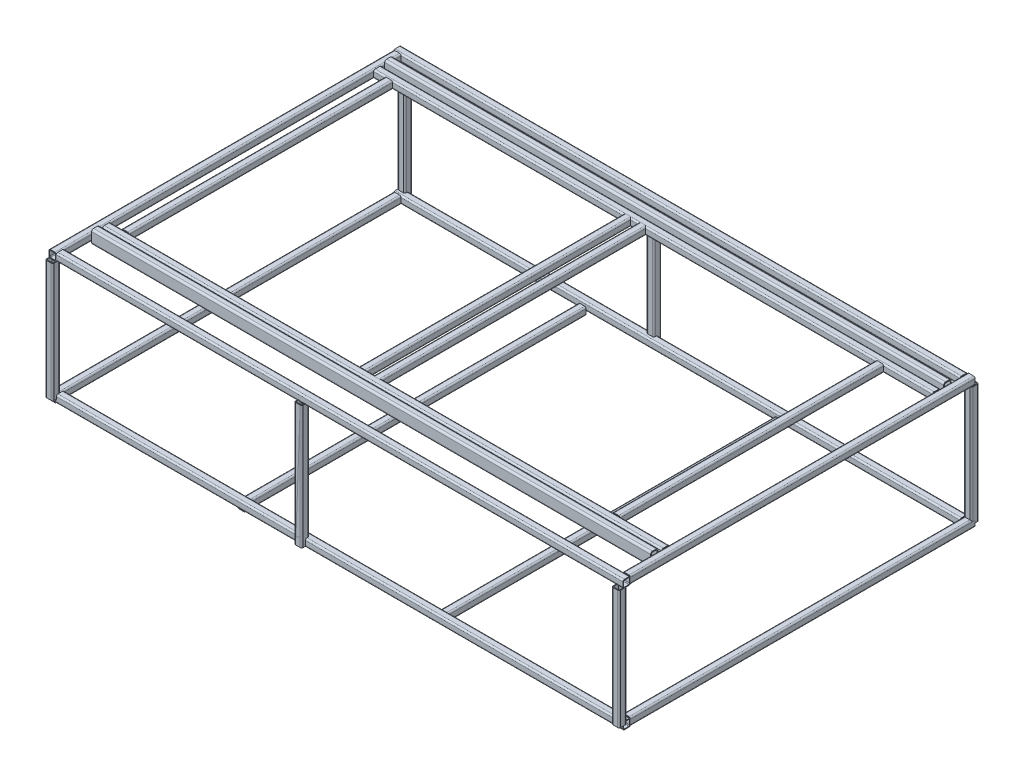
SolidWorks part; units mm, degrees
material "Beech"
ref_plane "Front Plane" through (0, 0, 0) normal (0, 0, 1) x (1, 0, 0)
ref_plane "Top Plane" through (0, 0, 0) normal (0, 1, 0) x (1, 0, 0)
ref_plane "Right Plane" through (0, 0, 0) normal (1, 0, 0) x (0, 0, -1)
sketch "Sketch1" plane through (0, 0, 0) normal (0, 1, 0) x (1, 0, 0)
  line L1 (-1500, 912.5) -> (1500, 912.5)
  line L2 (-1500, 912.5) -> (-1500, -912.5)
  line L3 (-1500, -912.5) -> (1500, -912.5)
  line L4 (1500, 912.5) -> (1500, -912.5)
  line L5 (-1500, 912.5) -> (1500, -912.5) construction
  line L6 (-1500, -912.5) -> (1500, 912.5) construction
  point P0 (0, 0)
  dimension "D1" = 3000
  dimension "D2" = 1825
other "Square tube 40 X 40 X 4(1)" corner treatment butt1
ref_plane "Plane1" through (-1500, 0, -912.5) normal (0, 0, 1) x (1, 0, 0)
sketch "Sketch13" plane through (-1500, 0, -912.5) normal (0, 0, 1) x (1, 0, 0)
  line L0 (-12, -16) -> (12, -16)
  line L1 (-16, -12) -> (-16, 12)
  line L2 (12, 16) -> (-12, 16)
  line L3 (16, 12) -> (16, -12)
  line L4 (-12, -20) -> (12, -20)
  line L5 (-20, -12) -> (-20, 12)
  line L6 (12, 20) -> (-12, 20)
  line L7 (20, 12) -> (20, -12)
  arc A0 (20, 12) -> (12, 20) centre (12, 12) ccw
  arc A1 (12, -20) -> (20, -12) centre (12, -12) ccw
  arc A2 (-20, -12) -> (-12, -20) centre (-12, -12) ccw
  arc A3 (-12, 20) -> (-20, 12) centre (-12, 12) ccw
  arc A4 (-12, 16) -> (-16, 12) centre (-12, 12) ccw
  arc A5 (16, 12) -> (12, 16) centre (12, 12) ccw
  arc A6 (12, -16) -> (16, -12) centre (12, -12) ccw
  arc A7 (-16, -12) -> (-12, -16) centre (-12, -12) ccw
  point P0 (-20, 0)
  point P1 (20, 0)
  point P2 (0, 20)
  point P3 (0, -20)
  point P4 (0, 0)
  point P5 (-20, -20)
  point P6 (20, -20)
  point P7 (20, 20)
  point P8 (-20, 20)
  point P33 (0, 0)
  dimension "D1" = 8
  dimension "Thickness" = 4
  dimension "V_leg" = 40
sketch "Sketch15" plane through (0, 0, 0) normal (0, 1, 0) x (1, 0, 0)
  line L0 (-1480, 826) -> (1480, 826)
  line L1 (-1480, -932.5) -> (-1480, 892.5) construction
  line L2 (1480, 932.5) -> (1480, -892.5) construction
  line L3 (-1480, -726) -> (1480, -726)
  line L4 (1520, -892.5) -> (-1480, -892.5) construction
  line L5 (-1520, 892.5) -> (1480, 892.5) construction
  dimension "D1" = 166.5
  dimension "D2" = 66.5
other "Rectangular tube 70 X 40 X 5(1)" corner treatment butt1
ref_plane "Plane2" through (-1480, 0, -826) normal (1, 0, 0) x (0, 0, -1)
sketch "Sketch17" plane through (-1480, 0, -826) normal (1, 0, 0) x (0, 0, -1)
  line L0 (-10, -30) -> (10, -30)
  line L1 (-15, -25) -> (-15, 25)
  line L2 (10, 30) -> (-10, 30)
  line L3 (15, 25) -> (15, -25)
  line L4 (-10, -35) -> (10, -35)
  line L5 (-20, -25) -> (-20, 25)
  line L6 (10, 35) -> (-10, 35)
  line L7 (20, 25) -> (20, -25)
  arc A0 (20, 25) -> (10, 35) centre (10, 25) ccw
  arc A1 (10, -35) -> (20, -25) centre (10, -25) ccw
  arc A2 (-20, -25) -> (-10, -35) centre (-10, -25) ccw
  arc A3 (-10, 35) -> (-20, 25) centre (-10, 25) ccw
  arc A4 (-10, 30) -> (-15, 25) centre (-10, 25) ccw
  arc A5 (15, 25) -> (10, 30) centre (10, 25) ccw
  arc A6 (10, -30) -> (15, -25) centre (10, -25) ccw
  arc A7 (-15, -25) -> (-10, -30) centre (-10, -25) ccw
  point P0 (0, 35)
  point P1 (20, 0)
  point P2 (0, -35)
  point P3 (-20, 0)
  point P4 (-20, 35)
  point P5 (20, 35)
  point P6 (20, -35)
  point P7 (-20, -35)
  point P8 (0, 0)
  point P33 (0, 0)
  dimension "D1" = 10
  dimension "Thickness" = 5
  dimension "V_leg" = 70
  dimension "H_leg" = 40
sketch "Sketch18" plane through (0, 0, 0) normal (0, 1, 0) x (1, 0, 0)
  line L0 (-1480, 767.5) -> (1480, 767.5)
  line L1 (-1480, -932.5) -> (-1480, 892.5) construction
  line L2 (1480, 932.5) -> (1480, -892.5) construction
  line L3 (1480, -667.5) -> (-1480, -667.5)
  line L5 (1480, 806) -> (-1480, 806) construction
  line L6 (1480, -706) -> (-1480, -706) construction
  dimension "D1" = 38.5
  dimension "D2" = 38.5
ref_plane "Plane3" through (-1480, 0, -767.5) normal (1, 0, 0) x (0, 0, -1)
other "Square tube 40 X 40 X 4(2)" corner treatment butt1
ref_plane "Plane4" through (-1480, 0, -767.5) normal (1, 0, 0) x (0, 0, -1)
sketch "Sketch110" plane through (-1480, 0, -767.5) normal (1, 0, 0) x (0, 0, -1)
  line L0 (-12, -16) -> (12, -16)
  line L1 (-16, -12) -> (-16, 12)
  line L2 (12, 16) -> (-12, 16)
  line L3 (16, 12) -> (16, -12)
  line L4 (-12, -20) -> (12, -20)
  line L5 (-20, -12) -> (-20, 12)
  line L6 (12, 20) -> (-12, 20)
  line L7 (20, 12) -> (20, -12)
  arc A0 (20, 12) -> (12, 20) centre (12, 12) ccw
  arc A1 (12, -20) -> (20, -12) centre (12, -12) ccw
  arc A2 (-20, -12) -> (-12, -20) centre (-12, -12) ccw
  arc A3 (-12, 20) -> (-20, 12) centre (-12, 12) ccw
  arc A4 (-12, 16) -> (-16, 12) centre (-12, 12) ccw
  arc A5 (16, 12) -> (12, 16) centre (12, 12) ccw
  arc A6 (12, -16) -> (16, -12) centre (12, -12) ccw
  arc A7 (-16, -12) -> (-12, -16) centre (-12, -12) ccw
  point P0 (-20, 0)
  point P1 (20, 0)
  point P2 (0, 20)
  point P3 (0, -20)
  point P4 (0, 0)
  point P5 (-20, -20)
  point P6 (20, -20)
  point P7 (20, 20)
  point P8 (-20, 20)
  point P33 (0, 0)
  dimension "D1" = 8
  dimension "Thickness" = 4
  dimension "V_leg" = 40
sketch "Sketch111" plane through (0, 0, 0) normal (0, 1, 0) x (1, 0, 0)
  line L0 (-1400, 747.5) -> (-1400, -647.5)
  line L1 (1480, 747.5) -> (-1480, 747.5) construction
  line L2 (1480, -647.5) -> (-1480, -647.5) construction
  line L3 (1200, 747.5) -> (1200, -647.5)
  line L5 (-1480, -932.5) -> (-1480, 892.5) construction
  line L6 (1480, 932.5) -> (1480, -892.5) construction
  dimension "D1" = 80
  dimension "D2" = 280
other "Square tube 40 X 40 X 4(3)" corner treatment butt1
ref_plane "Plane5" through (1200, 0, -747.5) normal (0, 0, 1) x (1, 0, 0)
sketch "Sketch112" plane through (1200, 0, -747.5) normal (0, 0, 1) x (1, 0, 0)
  line L0 (-12, -16) -> (12, -16)
  line L1 (-16, -12) -> (-16, 12)
  line L2 (12, 16) -> (-12, 16)
  line L3 (16, 12) -> (16, -12)
  line L4 (-12, -20) -> (12, -20)
  line L5 (-20, -12) -> (-20, 12)
  line L6 (12, 20) -> (-12, 20)
  line L7 (20, 12) -> (20, -12)
  arc A0 (20, 12) -> (12, 20) centre (12, 12) ccw
  arc A1 (12, -20) -> (20, -12) centre (12, -12) ccw
  arc A2 (-20, -12) -> (-12, -20) centre (-12, -12) ccw
  arc A3 (-12, 20) -> (-20, 12) centre (-12, 12) ccw
  arc A4 (-12, 16) -> (-16, 12) centre (-12, 12) ccw
  arc A5 (16, 12) -> (12, 16) centre (12, 12) ccw
  arc A6 (12, -16) -> (16, -12) centre (12, -12) ccw
  arc A7 (-16, -12) -> (-12, -16) centre (-12, -12) ccw
  point P0 (-20, 0)
  point P1 (20, 0)
  point P2 (0, 20)
  point P3 (0, -20)
  point P4 (0, 0)
  point P5 (-20, -20)
  point P6 (20, -20)
  point P7 (20, 20)
  point P8 (-20, 20)
  point P33 (0, 0)
  dimension "D1" = 8
  dimension "Thickness" = 4
  dimension "V_leg" = 40
sketch "Sketch113" plane through (0, 0, 0) normal (0, 1, 0) x (1, 0, 0)
  line L0 (-140, 755.5) -> (-140, -651.5)
  line L1 (1480, 755.5) -> (-1480, 755.5) construction
  line L2 (1480, -651.5) -> (-1480, -651.5) construction
  line L3 (-60, 755.5) -> (-60, -655.5)
  line L4 (1480, -655.5) -> (-1480, -655.5) construction
  line L5 (-1380, -647.5) -> (-1380, 747.5) construction
  line L6 (1180, -647.5) -> (1180, 747.5) construction
  dimension "D1" = 1240
  dimension "D2" = 1240
other "Square tube 40 X 40 X 4(4)" corner treatment butt1
ref_plane "Plane6" through (-60, 0, -755.5) normal (0, 0, 1) x (1, 0, 0)
sketch "Sketch114" plane through (-60, 0, -755.5) normal (0, 0, 1) x (1, 0, 0)
  line L0 (-12, -16) -> (12, -16)
  line L1 (-16, -12) -> (-16, 12)
  line L2 (12, 16) -> (-12, 16)
  line L3 (16, 12) -> (16, -12)
  line L4 (-12, -20) -> (12, -20)
  line L5 (-20, -12) -> (-20, 12)
  line L6 (12, 20) -> (-12, 20)
  line L7 (20, 12) -> (20, -12)
  arc A0 (20, 12) -> (12, 20) centre (12, 12) ccw
  arc A1 (12, -20) -> (20, -12) centre (12, -12) ccw
  arc A2 (-20, -12) -> (-12, -20) centre (-12, -12) ccw
  arc A3 (-12, 20) -> (-20, 12) centre (-12, 12) ccw
  arc A4 (-12, 16) -> (-16, 12) centre (-12, 12) ccw
  arc A5 (16, 12) -> (12, 16) centre (12, 12) ccw
  arc A6 (12, -16) -> (16, -12) centre (12, -12) ccw
  arc A7 (-16, -12) -> (-12, -16) centre (-12, -12) ccw
  point P0 (-20, 0)
  point P1 (20, 0)
  point P2 (0, 20)
  point P3 (0, -20)
  point P4 (0, 0)
  point P5 (-20, -20)
  point P6 (20, -20)
  point P7 (20, 20)
  point P8 (-20, 20)
  point P33 (0, 0)
  dimension "D1" = 8
  dimension "Thickness" = 4
  dimension "V_leg" = 40
sketch "Sketch115" plane through (0, 0, 932.5) normal (0, 0, 1) x (1, 0, 0)
  line L0 (-1500, -20) -> (-1500, -650)
  line L1 (-1512, -20) -> (-1488, -20) construction
  line L2 (-1520, 12) -> (-1520, -12) construction
  line L3 (-181, -12) -> (-181, -665)
  line L5 (1500, -20) -> (1500, -650)
  line L6 (1520, -20) -> (-1480, -20) construction
  line L7 (1520, 12) -> (1520, -12) construction
  line L9 (1520, -12) -> (-1480, -12) construction
  point P8 (-181, 0)
  point P9 (-181, -12)
  point P16 (-181, -35)
  point P17 (-181, -35)
  point P18 (-181, -35)
  point P19 (0, 0)
  point P21 (-181, 0)
  point P22 (0, 0)
  dimension "D1" = 20
  dimension "D2" = 630
  dimension "D4" = 630
  dimension "D5" = 1681
  dimension "D6" = 20
other "Square tube 40 X 40 X 4(5)" corner treatment butt1
ref_plane "Plane7" through (-1500, -20, 932.5) normal (0, -1, 0) x (1, 0, 0)
sketch "Sketch116" plane through (-1500, -20, 932.5) normal (0, -1, 0) x (1, 0, 0)
  line L0 (-12, -16) -> (12, -16)
  line L1 (-16, -12) -> (-16, 12)
  line L2 (12, 16) -> (-12, 16)
  line L3 (16, 12) -> (16, -12)
  line L4 (-12, -20) -> (12, -20)
  line L5 (-20, -12) -> (-20, 12)
  line L6 (12, 20) -> (-12, 20)
  line L7 (20, 12) -> (20, -12)
  arc A0 (20, 12) -> (12, 20) centre (12, 12) ccw
  arc A1 (12, -20) -> (20, -12) centre (12, -12) ccw
  arc A2 (-20, -12) -> (-12, -20) centre (-12, -12) ccw
  arc A3 (-12, 20) -> (-20, 12) centre (-12, 12) ccw
  arc A4 (-12, 16) -> (-16, 12) centre (-12, 12) ccw
  arc A5 (16, 12) -> (12, 16) centre (12, 12) ccw
  arc A6 (12, -16) -> (16, -12) centre (12, -12) ccw
  arc A7 (-16, -12) -> (-12, -16) centre (-12, -12) ccw
  point P0 (-20, 0)
  point P1 (20, 0)
  point P2 (0, 20)
  point P3 (0, -20)
  point P4 (0, 0)
  point P5 (-20, -20)
  point P6 (20, -20)
  point P7 (20, 20)
  point P8 (-20, 20)
  point P33 (0, 0)
  dimension "D1" = 8
  dimension "Thickness" = 4
  dimension "V_leg" = 40
sketch "Sketch117" plane through (0, 0, -932.5) normal (0, 0, -1) x (-1, 0, 0)
  line L0 (1500, -20) -> (1500, -650) construction
  line L1 (181, -12) -> (181, -665) construction
  line L2 (-1500, -20) -> (-1500, -650) construction
  line L3 (1500, -20) -> (1500, -650)
  line L4 (1520, -12) -> (1520, 12)
  line L5 (1520, 12) -> (-1480, 12)
  line L6 (-1480, 12) -> (-1480, -12)
  line L7 (-1480, -12) -> (1520, -12)
  line L8 (1520, -12) -> (1520, 12)
  line L9 (1520, 12) -> (-1480, 12)
  line L10 (-1480, 12) -> (-1480, -12)
  line L11 (-1480, -12) -> (1520, -12)
  line L12 (181, -12) -> (181, -665)
  line L13 (-1500, -20) -> (-1500, -650)
  dimension "D1" = 0
other "Square tube 40 X 40 X 4(6)" corner treatment butt1
ref_plane "Plane8" through (1500, -20, 932.5) normal (0, -1, 0) x (1, 0, 0)
sketch "Sketch118" plane through (1500, -20, 932.5) normal (0, -1, 0) x (1, 0, 0)
  line L0 (-12, -16) -> (12, -16)
  line L1 (-16, -12) -> (-16, 12)
  line L2 (12, 16) -> (-12, 16)
  line L3 (16, 12) -> (16, -12)
  line L4 (-12, -20) -> (12, -20)
  line L5 (-20, -12) -> (-20, 12)
  line L6 (12, 20) -> (-12, 20)
  line L7 (20, 12) -> (20, -12)
  arc A0 (20, 12) -> (12, 20) centre (12, 12) ccw
  arc A1 (12, -20) -> (20, -12) centre (12, -12) ccw
  arc A2 (-20, -12) -> (-12, -20) centre (-12, -12) ccw
  arc A3 (-12, 20) -> (-20, 12) centre (-12, 12) ccw
  arc A4 (-12, 16) -> (-16, 12) centre (-12, 12) ccw
  arc A5 (16, 12) -> (12, 16) centre (12, 12) ccw
  arc A6 (12, -16) -> (16, -12) centre (12, -12) ccw
  arc A7 (-16, -12) -> (-12, -16) centre (-12, -12) ccw
  point P0 (-20, 0)
  point P1 (20, 0)
  point P2 (0, 20)
  point P3 (0, -20)
  point P4 (0, 0)
  point P5 (-20, -20)
  point P6 (20, -20)
  point P7 (20, 20)
  point P8 (-20, 20)
  point P33 (0, 0)
  dimension "D1" = 8
  dimension "Thickness" = 4
  dimension "V_leg" = 40
other "Square tube 40 X 40 X 4(7)" corner treatment butt1
ref_plane "Plane9" through (1500, -20, -932.5) normal (0, -1, 0) x (-1, 0, 0)
sketch "Sketch119" plane through (1500, -20, -932.5) normal (0, -1, 0) x (-1, 0, 0)
  line L0 (-12, -16) -> (12, -16)
  line L1 (-16, -12) -> (-16, 12)
  line L2 (12, 16) -> (-12, 16)
  line L3 (16, 12) -> (16, -12)
  line L4 (-12, -20) -> (12, -20)
  line L5 (-20, -12) -> (-20, 12)
  line L6 (12, 20) -> (-12, 20)
  line L7 (20, 12) -> (20, -12)
  arc A0 (20, 12) -> (12, 20) centre (12, 12) ccw
  arc A1 (12, -20) -> (20, -12) centre (12, -12) ccw
  arc A2 (-20, -12) -> (-12, -20) centre (-12, -12) ccw
  arc A3 (-12, 20) -> (-20, 12) centre (-12, 12) ccw
  arc A4 (-12, 16) -> (-16, 12) centre (-12, 12) ccw
  arc A5 (16, 12) -> (12, 16) centre (12, 12) ccw
  arc A6 (12, -16) -> (16, -12) centre (12, -12) ccw
  arc A7 (-16, -12) -> (-12, -16) centre (-12, -12) ccw
  point P0 (-20, 0)
  point P1 (20, 0)
  point P2 (0, 20)
  point P3 (0, -20)
  point P4 (0, 0)
  point P5 (-20, -20)
  point P6 (20, -20)
  point P7 (20, 20)
  point P8 (-20, 20)
  point P33 (0, 0)
  dimension "D1" = 8
  dimension "Thickness" = 4
  dimension "V_leg" = 40
sketch "Sketch120" plane through (0, -650, 0) normal (0, -1, 0) x (1, 0, 0)
  line L0 (1500, -912.5) -> (1500, 912.5) construction
  line L1 (-1500, -912.5) -> (1500, -912.5) construction
  line L2 (-1500, -912.5) -> (-1500, 912.5) construction
  line L3 (-1500, 912.5) -> (1500, 912.5) construction
  line L4 (1512, 952.5) -> (1488, 952.5)
  line L5 (1480, 944.5) -> (1480, 920.5)
  line L6 (1488, 912.5) -> (1512, 912.5)
  line L7 (1520, 920.5) -> (1520, 944.5)
  line L8 (1512, 952.5) -> (1488, 952.5)
  line L9 (1480, 944.5) -> (1480, 920.5)
  line L10 (1488, 912.5) -> (1512, 912.5)
  line L11 (1520, 920.5) -> (1520, 944.5)
  line L12 (1500, -912.5) -> (1500, 912.5)
  line L13 (-1500, -912.5) -> (1500, -912.5)
  line L14 (-1500, -912.5) -> (-1500, 912.5)
  line L15 (-1500, 912.5) -> (1500, 912.5)
  arc A4 (1520, 944.5) -> (1512, 952.5) centre (1512, 944.5) ccw
  arc A5 (1488, 952.5) -> (1480, 944.5) centre (1488, 944.5) ccw
  arc A6 (1480, 920.5) -> (1488, 912.5) centre (1488, 920.5) ccw
  arc A7 (1512, 912.5) -> (1520, 920.5) centre (1512, 920.5) ccw
  arc A8 (1520, 944.5) -> (1512, 952.5) centre (1512, 944.5) ccw
  arc A9 (1488, 952.5) -> (1480, 944.5) centre (1488, 944.5) ccw
  arc A10 (1480, 920.5) -> (1488, 912.5) centre (1488, 920.5) ccw
  arc A11 (1512, 912.5) -> (1520, 920.5) centre (1512, 920.5) ccw
  dimension "D1" = 0
other "Square tube 40 X 40 X 4(8)" corner treatment butt1
ref_plane "Plane10" through (-1500, -650, 912.5) normal (1, 0, 0) x (0, 0, 1)
sketch "Sketch121" plane through (-1500, -650, 912.5) normal (1, 0, 0) x (0, 0, 1)
  line L0 (-12, -16) -> (12, -16)
  line L1 (-16, -12) -> (-16, 12)
  line L2 (12, 16) -> (-12, 16)
  line L3 (16, 12) -> (16, -12)
  line L4 (-12, -20) -> (12, -20)
  line L5 (-20, -12) -> (-20, 12)
  line L6 (12, 20) -> (-12, 20)
  line L7 (20, 12) -> (20, -12)
  arc A0 (20, 12) -> (12, 20) centre (12, 12) ccw
  arc A1 (12, -20) -> (20, -12) centre (12, -12) ccw
  arc A2 (-20, -12) -> (-12, -20) centre (-12, -12) ccw
  arc A3 (-12, 20) -> (-20, 12) centre (-12, 12) ccw
  arc A4 (-12, 16) -> (-16, 12) centre (-12, 12) ccw
  arc A5 (16, 12) -> (12, 16) centre (12, 12) ccw
  arc A6 (12, -16) -> (16, -12) centre (12, -12) ccw
  arc A7 (-16, -12) -> (-12, -16) centre (-12, -12) ccw
  point P0 (-20, 0)
  point P1 (20, 0)
  point P2 (0, 20)
  point P3 (0, -20)
  point P4 (0, 0)
  point P5 (-20, -20)
  point P6 (20, -20)
  point P7 (20, 20)
  point P8 (-20, 20)
  point P33 (0, 0)
  dimension "D1" = 8
  dimension "Thickness" = 4
  dimension "V_leg" = 40
sketch "Sketch122" plane through (0, -670, 0) normal (0, -1, 0) x (1, 0, 0)
  line L0 (-520, 912.5) -> (-520, -892.5)
  line L1 (-1500, 912.5) -> (1500, 912.5) construction
  line L2 (-1520, -892.5) -> (1480, -892.5) construction
  line L3 (520, 892.5) -> (520, -896.5)
  line L4 (1520, 892.5) -> (-1480, 892.5) construction
  line L5 (-1520, -896.5) -> (1480, -896.5) construction
  line L8 (-1480, 932.5) -> (-1480, -892.5) construction
  line L9 (1480, -932.5) -> (1480, 892.5) construction
  dimension "D1" = 960
  dimension "D2" = 960
other "Square tube 40 X 40 X 4(9)" corner treatment butt1
ref_plane "Plane11" through (520, -670, 892.5) normal (0, 0, -1) x (1, 0, 0)
sketch "Sketch123" plane through (520, -670, 892.5) normal (0, 0, -1) x (1, 0, 0)
  line L0 (-12, -16) -> (12, -16)
  line L1 (-16, -12) -> (-16, 12)
  line L2 (12, 16) -> (-12, 16)
  line L3 (16, 12) -> (16, -12)
  line L4 (-12, -20) -> (12, -20)
  line L5 (-20, -12) -> (-20, 12)
  line L6 (12, 20) -> (-12, 20)
  line L7 (20, 12) -> (20, -12)
  arc A0 (20, 12) -> (12, 20) centre (12, 12) ccw
  arc A1 (12, -20) -> (20, -12) centre (12, -12) ccw
  arc A2 (-20, -12) -> (-12, -20) centre (-12, -12) ccw
  arc A3 (-12, 20) -> (-20, 12) centre (-12, 12) ccw
  arc A4 (-12, 16) -> (-16, 12) centre (-12, 12) ccw
  arc A5 (16, 12) -> (12, 16) centre (12, 12) ccw
  arc A6 (12, -16) -> (16, -12) centre (12, -12) ccw
  arc A7 (-16, -12) -> (-12, -16) centre (-12, -12) ccw
  point P0 (-20, 0)
  point P1 (20, 0)
  point P2 (0, 20)
  point P3 (0, -20)
  point P4 (0, 0)
  point P5 (-20, -20)
  point P6 (20, -20)
  point P7 (20, 20)
  point P8 (-20, 20)
  point P33 (0, 0)
  dimension "D1" = 8
  dimension "Thickness" = 4
  dimension "V_leg" = 40
